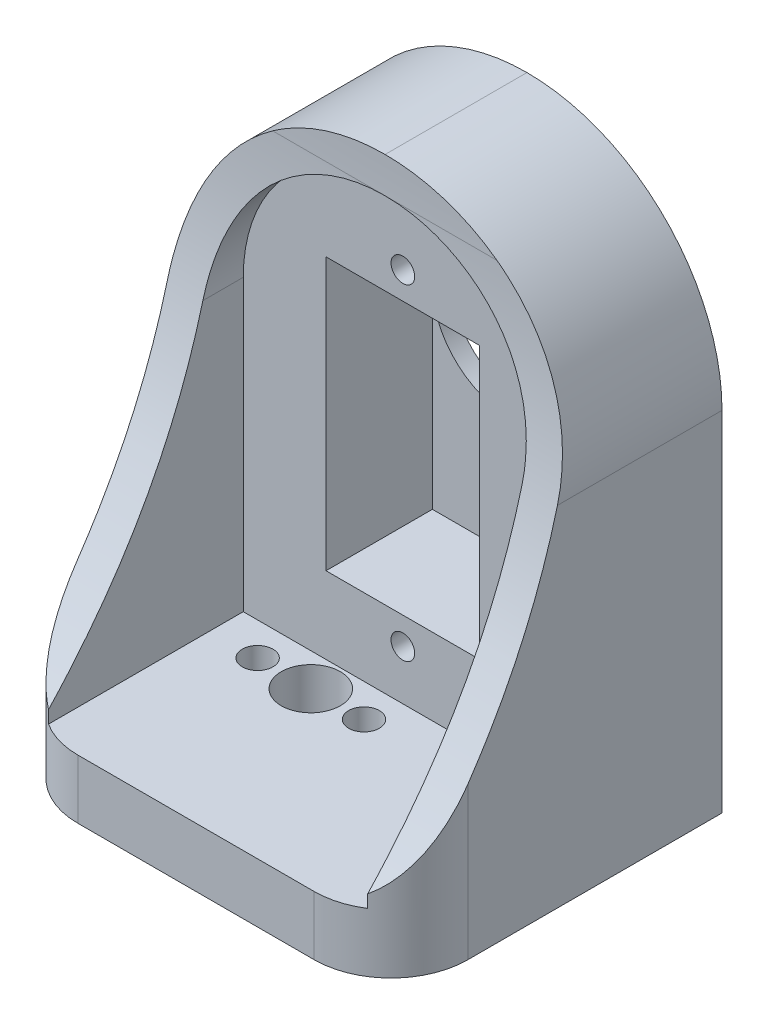
SolidWorks part; units mm, degrees
ref_plane "Front Plane" through (0, 0, 0) normal (0, 0, 1) x (1, 0, 0)
ref_plane "Top Plane" through (0, 0, 0) normal (0, 1, 0) x (1, 0, 0)
ref_plane "Right Plane" through (0, 0, 0) normal (1, 0, 0) x (0, 0, -1)
sketch "Sketch1" plane through (0, 0, 0) normal (0, 1, 0) x (1, 0, 0)
  line L1 (-16500, 14000) -> (16500, 14000)
  line L2 (-16500, 14000) -> (-16500, -14000)
  line L3 (-16500, -14000) -> (16500, -14000)
  line L4 (16500, 14000) -> (16500, -14000)
  line L5 (-16500, 14000) -> (16500, -14000) construction
  line L6 (-16500, -14000) -> (16500, 14000) construction
  point P0 (0, 0)
  dimension "D1" = 33000
  dimension "D2" = 28000
extrude "Boss-Extrude1" add sketch "Sketch1" along normal blind 46000
sketch "Sketch2" plane through (16500, 0, 0) normal (1, 0, 0) x (0, 0, -1)
  line L0 (-14000, 0) -> (14000, 0) construction
  line L1 (-14000, 46000) -> (3500, 46000)
  line L2 (-14000, 46000) -> (-14000, 5000)
  line L3 (-14000, 5000) -> (3500, 5000)
  line L4 (3500, 46000) -> (3500, 5000)
  line L9 (14000, 46000) -> (14000, 0) construction
  point P5 (-5751.634, 19859.3051)
  point P6 (-5250, 5000)
  point P9 (0, 0)
  dimension "D1" = 5000
  dimension "D2" = 10500
extrude "Cut-Extrude1" cut sketch "Sketch2" against normal blind 46000
sketch "Sketch4" plane through (16500, 0, 0) normal (1, 0, 0) x (0, 0, -1)
  line L0 (3500, 46000) -> (2000, 46000)
  line L1 (3500, 46000) -> (3500, 5000)
  line L4 (3500, 5000) -> (-14000, 5000)
  spline S0 degree 2 poles (-14000, 5000) (2293.5638, 21561.0186) (2000, 46000) knots 0 0 0 1 1 1
  dimension "D1" = 1500
extrude "Boss-Extrude2" add sketch "Sketch4" against normal blind 3000
mirror "Mirror1" about plane through (0, 0, 0) normal (1, 0, 0) of "Boss-Extrude2"
sketch "Sketch5" plane through (13500, 0, 0) normal (-1, 0, 0) x (0, 0, 1)
  line L0 (-3500, 43000) -> (-1972.6456, 43000)
  line L3 (-3500, 46000) -> (-3500, 5000)
  line L4 (-3500, 5000) -> (14000, 5000)
  line L5 (-2000, 46000) -> (-3500, 46000)
  line L6 (-3500, 46000) -> (-3500, 5000)
  line L7 (-3500, 5000) -> (14000, 5000)
  line L8 (-2000, 46000) -> (-3500, 46000)
  parabola Q1 (14000, 5000) -> (-2000, 46000) focus (27040.8203, 31342.1698) apex (3340.8563, 20086.0054)
  parabola Q2 (14000, 5000) -> (-2000, 46000) focus (27040.8203, 31342.1698) apex (3340.8563, 20086.0054)
  line M6 (-3500, 46000) -> (-3500, 5000)
  spline M8 degree 2 poles (-2000, 46000) (-2293.5638, 21561.0186) (14000, 5000) knots 0 0 0 1 1 1
  line M9 (-2000, 46000) -> (-3500, 46000)
  dimension "D2" = 3000
  dimension "D1" = 0
extrude "Boss-Extrude5" add sketch "Sketch5" along normal up to surface (27000 mm away) contours L0 M6 M8 M9 region at (13500, 44495.4716, -2748.4692) up to face at (-13500, 30625, 1437.5)
fillet "Fillet2" radius 13500 2 edges
fillet "Fillet3" radius 16500 2 edges at (16500, 46000, -8000) (-16500, 46000, -8000)
fillet "Fillet4" radius 6500 2 edges at (16500, 2500, 14000) (-16500, 2500, 14000)
sketch "Sketch6" plane through (0, 0, -3500) normal (0, 0, 1) x (1, 0, 0)
  line L0 (-10000, 5000) -> (10000, 5000) construction
  line L1 (-6500, 34500) -> (6500, 34500)
  line L2 (-6500, 34500) -> (-6500, 11500)
  line L3 (-6500, 11500) -> (6500, 11500)
  line L4 (6500, 34500) -> (6500, 11500)
  line L5 (-6500, 34500) -> (6500, 11500) construction
  line L6 (-6500, 11500) -> (6500, 34500) construction
  point P0 (0, 23000)
  point P5 (0, 0)
  dimension "D1" = 13000
  dimension "D2" = 23000
  dimension "D3" = 6500
extrude "Cut-Extrude2" cut sketch "Sketch6" against normal blind 9000
sketch "Sketch8" plane through (0, 0, -12500) normal (0, 0, 1) x (1, 0, 0)
  line L0 (6500, 34500) -> (-6500, 34500) construction
  circle A0 centre (0, 28000) radius 6500
  point P6 (454.0764, 28032.6828)
  point P7 (0, 0)
  dimension "D1" = 13000
  dimension "D2" = 6500
extrude "Cut-Extrude3" cut sketch "Sketch8" against normal blind 9000
sketch "Sketch9" plane through (0, 0, -3500) normal (0, 0, 1) x (1, 0, 0)
  line L0 (0, 36800) -> (0, 9200) construction
  line L1 (6500, 34500) -> (-6500, 34500) construction
  circle A0 centre (0, 36800) radius 1000
  circle A1 centre (0, 9200) radius 1000
  dimension "D1" = 2000
  dimension "D2" = 2300
  dimension "D3" = 27600
extrude "Cut-Extrude4" cut sketch "Sketch9" against normal blind 8000
sketch "Sketch10" plane through (0, 5000, 0) normal (0, 1, 0) x (1, 0, 0)
  line L0 (-16500, 81.3515) -> (-16500, -7500) construction
  circle A0 centre (-500, 714.0213) radius 1300
  circle A1 centre (-5000, 714.0213) radius 2500
  circle A2 centre (-9500, 714.0213) radius 1300
  dimension "D1" = 2600
  dimension "D2" = 5000
  dimension "D3" = 4500
  dimension "D4" = 9000
  dimension "D5" = 11500
extrude "Cut-Extrude5" cut sketch "Sketch10" against normal through all
